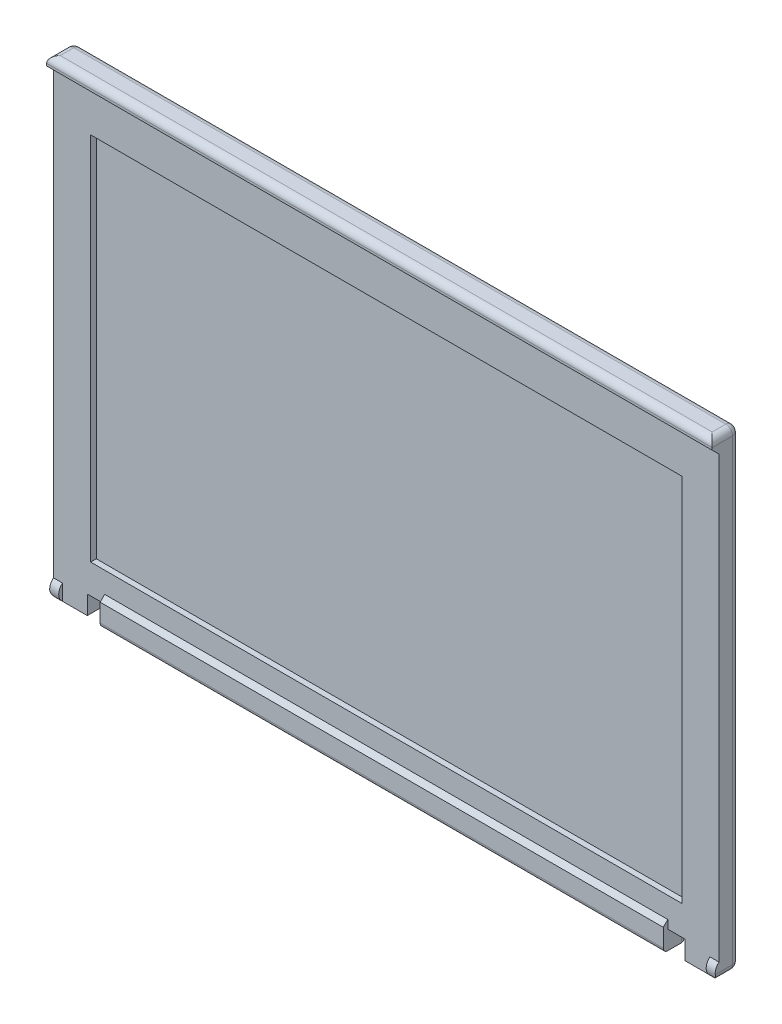
SolidWorks part; units mm, degrees
material "ABS"
ref_plane "Front Plane" through (0, 0, 0) normal (0, 0, 1) x (1, 0, 0)
ref_plane "Top Plane" through (0, 0, 0) normal (0, 1, 0) x (1, 0, 0)
ref_plane "Right Plane" through (0, 0, 0) normal (1, 0, 0) x (0, 0, -1)
sketch "Sketch1" plane through (0, 0, 0) normal (0, 0, 1) x (1, 0, 0)
  line L0 (-147.5, 0) -> (0, 0) construction
  line L1 (-147.5, 104.5) -> (147.5, 104.5)
  line L2 (-147.5, 104.5) -> (-147.5, -104.5)
  line L3 (-147.5, -104.5) -> (147.5, -104.5)
  line L4 (147.5, 104.5) -> (147.5, -104.5)
  line L5 (0, 104.5) -> (0, 0) construction
  dimension "D1" = 209
  dimension "D2" = 295
extrude "Boss-Extrude1" add sketch "Sketch1" along normal blind 9
sketch "Sketch2" plane through (0, 0, 9) normal (0, 0, 1) x (1, 0, 0)
  line L0 (147.5, 104.5) -> (-147.5, 104.5) construction
  line L1 (-131, 80.8) -> (131, 80.8)
  line L2 (-131, 80.8) -> (-131, -83.2)
  line L3 (-131, -83.2) -> (131, -83.2)
  line L4 (131, 80.8) -> (131, -83.2)
  line L6 (0, 80.8) -> (0, 0) construction
  dimension "D1" = 262
  dimension "D2" = 164
  dimension "D3" = 23.7
extrude "Cut-Extrude1" cut sketch "Sketch2" against normal blind 2.5
sketch "Sketch3" plane through (147.5, 0, 0) normal (1, 0, 0) x (0, 0, -1)
  line L0 (0, -104.5) -> (0, 104.5) construction
  line L1 (-9, 104.5) -> (-12, 104.5)
  line L2 (-9, 104.5) -> (-9, 101.5)
  line L3 (-9, 101.5) -> (-12, 101.5)
  line L4 (-12, 104.5) -> (-12, 101.5)
  dimension "D1" = 12
  dimension "D2" = 3
extrude "Boss-Extrude2" add sketch "Sketch3" against normal blind 295
chamfer "Chamfer1" distance 4 angle 45 1 edges
sketch "Sketch4" plane through (0, 0, 9) normal (0, 0, 1) x (1, 0, 0)
  line L0 (-147.5, -104.5) -> (147.5, -104.5) construction
  line L1 (-132.5, -104.5) -> (-124.8, -104.5)
  line L2 (-132.5, -104.5) -> (-132.5, -96.2)
  line L3 (-132.5, -96.2) -> (-124.8, -96.2)
  line L4 (-124.8, -104.5) -> (-124.8, -96.2)
  line L5 (0, -104.5) -> (0, -83.2) construction
  line L6 (-131, -83.2) -> (131, -83.2) construction
  line L7 (-147.5, 97.5) -> (-147.5, -104.5) construction
  line L8 (-131, -83.2) -> (131, -83.2) construction
  line L9 (124.8, -104.5) -> (124.8, -96.2)
  line L10 (132.5, -96.2) -> (124.8, -96.2)
  line L11 (132.5, -104.5) -> (132.5, -96.2)
  line L12 (132.5, -104.5) -> (124.8, -104.5)
  dimension "D1" = 15
  dimension "D2" = 7.7
  dimension "D3" = 13
extrude "Cut-Extrude2" cut sketch "Sketch4" against normal blind 250
sketch "Sketch5" plane through (147.5, 0, 0) normal (1, 0, 0) x (0, 0, -1)
  line L1 (-9, -104.5) -> (-9, 97.5) construction
  line L2 (-9, -104.5) -> (-9, -97.5)
  arc A0 (-9, -97.5) -> (-9, -104.5) centre (-6.1716, -101) ccw
  dimension "D2" = 4.5
  dimension "D1" = 7
extrude "Boss-Extrude3" add sketch "Sketch5" against normal blind 4
mirror "Mirror1" about plane through (0, 0, 0) normal (1, 0, 0) of "Boss-Extrude3"
sketch "Sketch6" plane through (0, 0, 9) normal (0, 0, 1) x (1, 0, 0)
  line L0 (-124.8, -104.5) -> (124.8, -104.5) construction
  line L1 (-124.8, -104.5) -> (124.8, -104.5)
  line L2 (-124.8, -104.5) -> (-124.8, -94.5)
  line L3 (-124.8, -94.5) -> (124.8, -94.5)
  line L4 (124.8, -104.5) -> (124.8, -94.5)
  dimension "D1" = 10
extrude "Boss-Extrude4" add sketch "Sketch6" along normal blind 2
chamfer "Chamfer2" distance 2 angle 45 1 edges at (0, -94.5, 9)
fillet "Fillet1" radius 2 1 edges at (0, -104.5, 11)
fillet "Fillet2" radius 3 17 edges at (132.5, -100.35, 0) (140, -104.5, 0) (147.5, 0, 0) (0, 104.5, 0) (-147.5, 0, 0) (-140, -104.5, 0) (-132.5, -100.35, 0) (-128.65, -96.2, 0) (-124.8, -100.35, 0) (0, -104.5, 0) (124.8, -100.35, 0) (128.65, -96.2, 0) (147.5, 104.5, 6) (0, 104.5, 12) (-147.5, 104.5, 6) (-147.5, -104.5, 4.5) (147.5, -104.5, 4.5)
